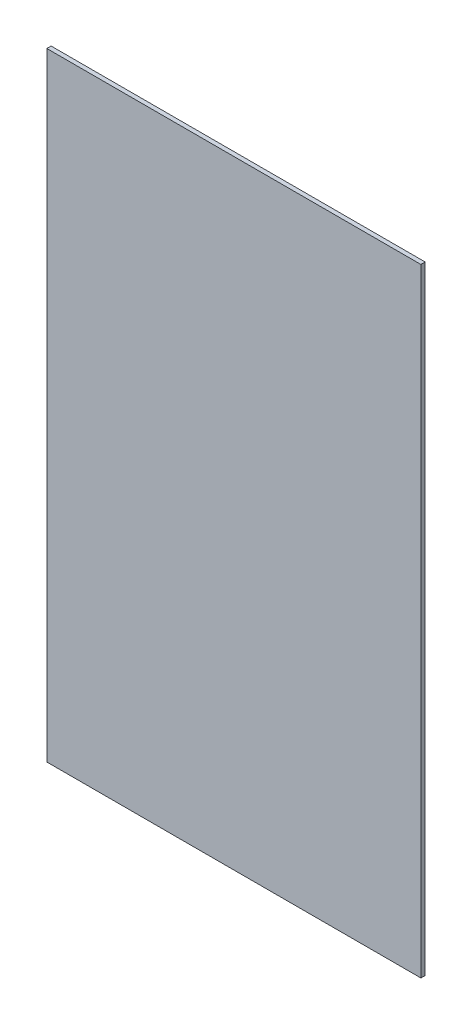
SolidWorks part; units mm, degrees
ref_plane "Спереди" through (0, 0, 0) normal (0, 0, 1) x (1, 0, 0)
ref_plane "Сверху" through (0, 0, 0) normal (0, 1, 0) x (1, 0, 0)
ref_plane "Справа" through (0, 0, 0) normal (1, 0, 0) x (0, 0, -1)
sketch "Эскиз1" plane through (0, 0, 0) normal (0, 0, 1) x (1, 0, 0)
  line L1 (171.206, 664.8747) -> (-352.794, 664.8747)
  line L2 (171.206, 664.8747) -> (171.206, -200.7253)
  line L3 (171.206, -200.7253) -> (-352.794, -200.7253)
  line L4 (-352.794, 664.8747) -> (-352.794, -200.7253)
  line L5 (-352.794, -206.7253) -> (-352.794, 664.8747) construction
  line L6 (-346.794, -200.7253) -> (171.206, -200.7253) construction
  line L7 (171.206, 664.8747) -> (-346.794, 664.8747) construction
  line L8 (171.206, 292.8747) -> (171.206, 664.8747) construction
extrude "Бобышка-Вытянуть1" add sketch "Эскиз1" against normal blind 6
equation "\"Ширина груза\"= 420"
equation "\"Глубина груза\"= 490"
equation "\"Высота груза\"= 297"
equation "\"Ширина ячейки\"= \"Ширина груза\" + 10"
equation "\"Глубина ячейки\"= \"Глубина груза\" + 10"
equation "\"Высота ячейки\"= \"Высота груза\" + 10 + 13"
equation "\"Колво ячеек ширина\"= 2"
equation "\"Колво ячеек высота\"= 2"
equation "\"Толщина стенки\" = 6"
equation "\"Крепление дверцы\"= 5 "
equation "\"Ширина рейки\"= \"Толщина шестерни\""
equation "\"Высота рейки\"= 20"
equation "\"Высота пола\"= \"Толщина стенки\" * 2"
equation "\"Колво полозьев\"= 5"
equation "\"Отступ рейки\"= 20"
equation "\"Глубина каретки\"= \"Глубина ячейки\" + 30 + \"Мотор Y высота корпуса\" + 20"
equation "\"Длинна рейки\"= ( \"Ширина ячейки\" + \"Толщина стенки\" + \"Крепление дверцы\" ) * \"Колво ячеек ширина\" + \"Ширина ячейки выгрузки\" * \"Колво выгрузки\" + \"Толщина стенки\""
equation "\"Отступ шпильки\"= 26"
equation "\"Диаметр шпильки\"= 5"
equation "\"Длинна шпильки\"= ( \"Высота ячейки\" + \"Толщина стенки\" + \"Высота пола\" ) * \"Колво ячеек высота\" + ( \"Толщина стенки\" + \"Отступ рейки\" ) * 2 "
equation "\"Ширина пластины\"= 50  "
equation "\"Высота зона выгрузки\"= \"Высота ячейки\" * 2 + \"Толщина стенки\" * 2"
equation "\"Колво выгрузки\"= 1"
equation "\"Ширина ячейки выгрузки\"= \"Ширина ячейки\" + \"Толщина стенки\" + \"Отступ крепления мотора фиксации\"*2"
equation "\"Отступ крепления мотора фиксации\" = 30"
equation "\"Мотор X ширина корпуса\"= 42.3"
equation "\"Мотор X высота корпуса\"= 42.3"
equation "\"Мотор X длина корпуса\"= 40"
equation "\"Мотор X вылет вала\"= 19.8"
equation "\"Мотор Y ширина корпуса\"= 42.3"
equation "\"Мотор Y высота корпуса\"= 42.3"
equation "\"Мотор Y длина корпуса\"= 48"
equation "\"Мотор Y вылет вала\"= 30"
equation "\"Мотор Z ширина корпуса\"= 42"
equation "\"Мотор Z высота корпуса\"= 42"
equation "\"Мотор Z длина корпуса\"= 40"
equation "\"Мотор Z вылет вала\"= 23"
equation "\"Мотор диаметр вала ПРЕДВ\"= 5"
equation "\"Мотор шаг крепления ПРЕДВ\"= 31"
equation "\"Мотор диаметр отверстий ПРЕДВ\"= 3"
equation "\"Мотор глубина отверстий ПРЕДВ\"= 4.5"
equation "\"Мотор диаметр буртика ПРЕДВ\"= 22"
equation "\"Мотор высота буртика ПРЕДВ\"= 2"
equation "\"Мотор диаметр шкива ПРЕДВ\"= 16"
equation "\"Мотор длина шкива ПРЕДВ\"= 12"
equation "\"Мотор отступ шкива ПРЕДВ\"= 5"
equation "\"Мотор X шаг градусов\"= 1.8"
equation "\"Мотор Y шаг градусов\"= 1.8"
equation "\"Мотор Z шаг градусов\"= 1.8"
equation "\"Мотор Y диаметр ротора\"= 25.78"
equation "\"Толщина шестерни\"= 10"
equation "\"D1@Бобышка-Вытянуть1\"=\"Толщина стенки\""
